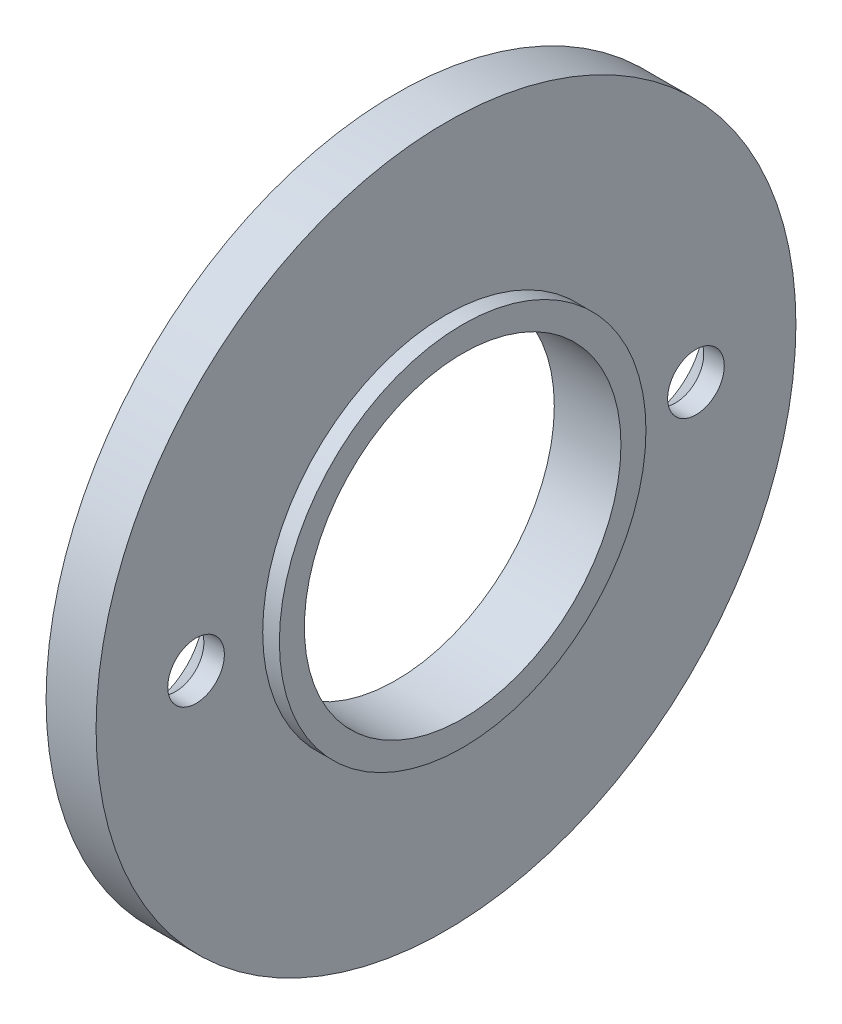
SolidWorks part; units mm, degrees
ref_plane "Front Plane" through (0, 0, 0) normal (0, 0, 1) x (1, 0, 0)
ref_plane "Top Plane" through (0, 0, 0) normal (0, 1, 0) x (1, 0, 0)
ref_plane "Right Plane" through (0, 0, 0) normal (1, 0, 0) x (0, 0, -1)
ref_axis "X-Axis" through (88.99, 0, 0) along (-1, 0, 0)
ref_axis "Y-Axis" through (0, 0, -88.99) along (0, 0, 1)
ref_axis "Z-Axis" through (0, -55, 0) along (0, 1, 0)
sketch "Sketch1" plane through (0, 0, 0) normal (0, 1, 0) x (1, 0, 0)
  line L0 (88.99, 0) -> (-88.99, 0) construction
  line L1 (-1.5, 21) -> (1.5, 21)
  line L2 (-1.5, 21) -> (-1.5, 9.5)
  line L4 (1.5, 21) -> (1.5, 11)
  line L5 (-1.5, 9.5) -> (2.5, 9.5)
  line L7 (1.5, 11) -> (2.5, 11)
  line L8 (2.5, 9.5) -> (2.5, 11)
  line L9 (0, 88.99) -> (0, -88.99) construction
  point P1 (0, 21)
  dimension "D1" = 11
  dimension "D2" = 1.5
  dimension "D3" = 10
  dimension "D4" = 3
  dimension "D5" = 1
revolve "Revolve1" add sketch "Sketch1" angle 360 about axis through (88.99, 0, 0) along (-1, 0, 0)
sketch "Sketch2" plane through (-1.5, 0, 0) normal (-1, 0, 0) x (0, 0, 1)
  line L0 (-88.99, 0) -> (88.99, 0) construction
  point P0 (15, 0)
  point P5 (-15, 0)
  dimension "D1" = 15
  dimension "D2" = 15
hole_wizard "CSK for M3 Hex Socket Countersunk Head Screw1" positions "3DSketch1" profile "Sketch3" countersink size "M3" standard "DIN" end condition up to next
sketch3d "3DSketch1"
  point P0 (-1.5, 0, 15)
  point P3 (-1.5, 0, -15)
sketch "Sketch3" plane through (-1.5, 0, 15) normal (0, 1, 0) x (0, 0, 1)
  line L0 (0, 0) -> (0, 3)
  line L1 (0, 3) -> (1.7, 3)
  line L2 (1.7, 3) -> (1.7, 1.77)
  line L3 (1.7, 1.77) -> (3.47, 0)
  line L5 (3.47, 0) -> (0, 0)
  line L6 (-1.7, 1.77) -> (-3.47, 0) construction
  line L11 (0, -6.35) -> (0, 107.95) construction
  dimension "Thru Hole Dia." = 3.4
  dimension "Thru Hole Depth" = 3
  dimension "Near C'Sink Dia." = 6.94
  dimension "Near C'Sink Angle" = 90
